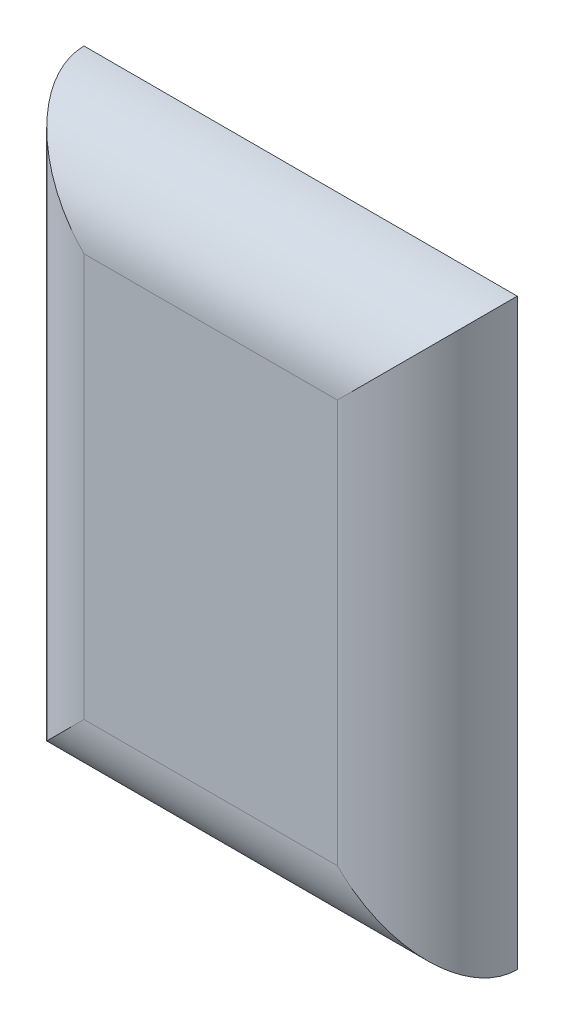
SolidWorks part; units mm, degrees
material "Cedar"
ref_plane "Front Plane" through (0, 0, 0) normal (0, 0, 1) x (1, 0, 0)
ref_plane "Top Plane" through (0, 0, 0) normal (0, 1, 0) x (1, 0, 0)
ref_plane "Right Plane" through (0, 0, 0) normal (1, 0, 0) x (0, 0, -1)
sketch "Sketch1" plane through (0, 0, 0) normal (0, 0, 1) x (1, 0, 0)
  line L0 (0, 44.3214) -> (0, -80.1884) construction
  line L1 (-59.9492, 0) -> (97.8658, 0) construction
  line L3 (-130, 175) -> (130, 175)
  line L4 (-130, 175) -> (-130, -175)
  line L5 (-130, -175) -> (130, -175)
  line L6 (130, 175) -> (130, -175)
  dimension "D1" = 260
  dimension "D2" = 350
extrude "Boss-Extrude1" add sketch "Sketch1" along normal blind 54
fillet "Fillet1" radius 54 4 edges at (130, 0, 54) (-130, 0, 54) (0, -175, 54) (0, 175, 54)
